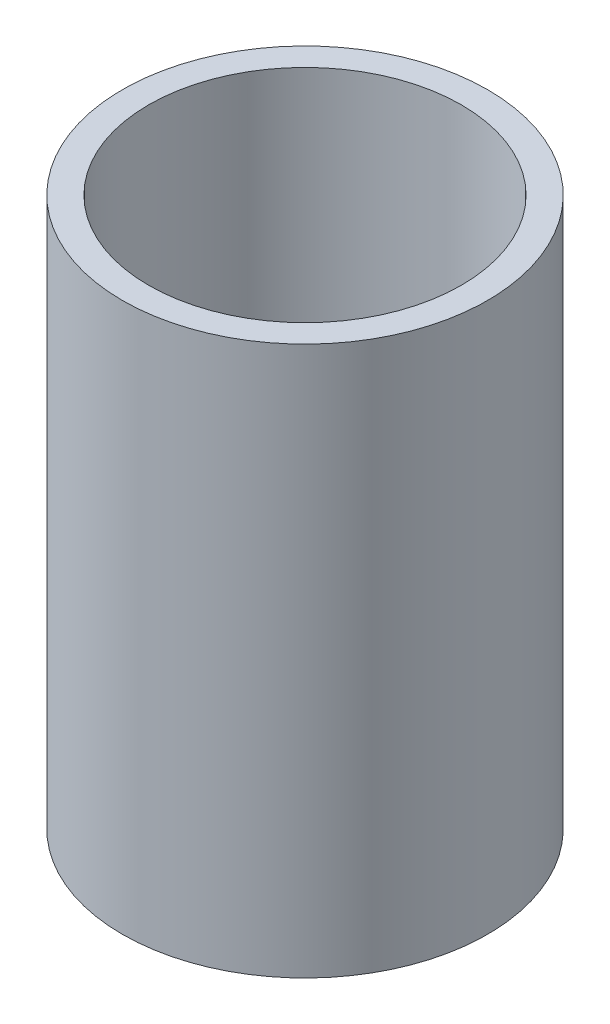
SolidWorks part; units mm, degrees
ref_plane "Front Plane" through (0, 0, 0) normal (0, 0, 1) x (1, 0, 0)
ref_plane "Top Plane" through (0, 0, 0) normal (0, 1, 0) x (1, 0, 0)
ref_plane "Right Plane" through (0, 0, 0) normal (1, 0, 0) x (0, 0, -1)
sketch "Sketch1" plane through (0, 0, 0) normal (0, 1, 0) x (1, 0, 0)
  circle A0 centre (0, 0) radius 35
  dimension "SLEEVE_OD" = 70
extrude "Boss-Extrude1" add sketch "Sketch1" along normal blind 105.2275
sketch "Sketch2" plane through (0, 0, 0) normal (0, 1, 0) x (1, 0, 0)
  circle A0 centre (0, 0) radius 29.9679
  dimension "BORE_D" = 59.9358
extrude "Cut-Extrude1" cut sketch "Sketch2" along normal through all
chamfer "Chamfer1" distance 3.1584 angle 54.263 rebuild error yes
